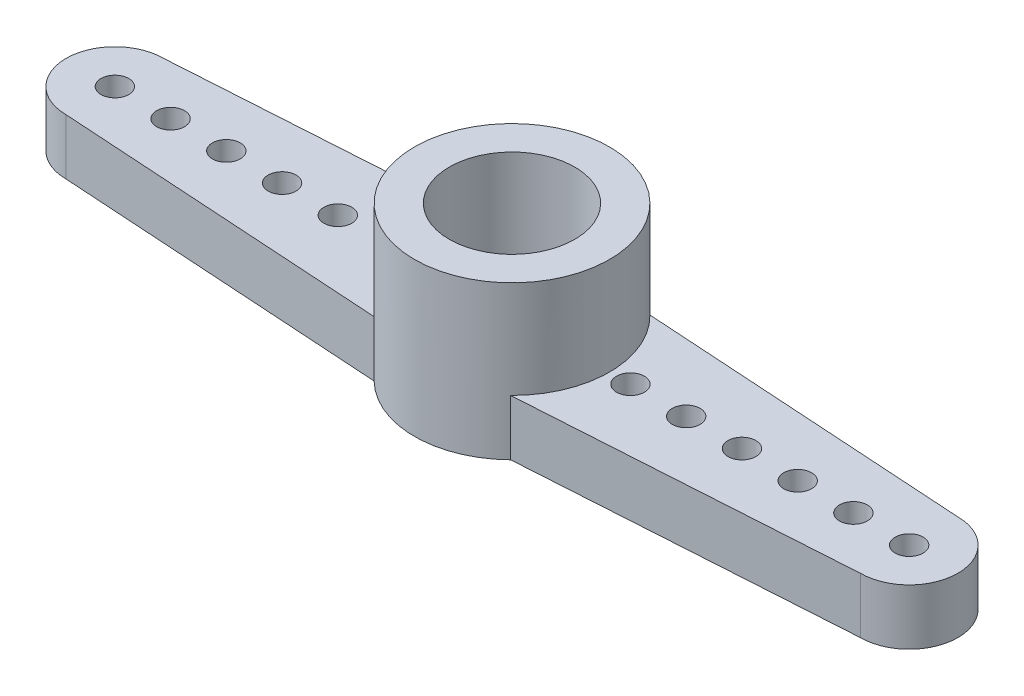
SolidWorks part; units mm, degrees
material "Nylon 101"
ref_plane "Front Plane" through (0, 0, 0) normal (0, 0, 1) x (1, 0, 0)
ref_plane "Top Plane" through (0, 0, 0) normal (0, 1, 0) x (1, 0, 0)
ref_plane "Right Plane" through (0, 0, 0) normal (1, 0, 0) x (0, 0, -1)
sketch "Sketch1" plane through (0, 0, 0) normal (0, 1, 0) x (1, 0, 0)
  line L0 (-16, 0) -> (16, 0) construction
  line L1 (-14.25, 1.75) -> (-2.4495, 2.5)
  line L2 (-14.25, -1.75) -> (-2.4495, -2.5)
  line L3 (-2.4495, 2.5) -> (-2.4495, -2.5) construction
  line L4 (14.25, 1.75) -> (2.4495, 2.5)
  line L5 (14.25, -1.75) -> (2.4495, -2.5)
  line L6 (2.4495, -2.5) -> (2.4495, 2.5) construction
  arc A0 (-2.4495, -2.5) -> (2.4495, -2.5) centre (0, 0) ccw
  arc A1 (14.25, -1.75) -> (14.25, 1.75) centre (14.25, 0) ccw
  arc A2 (-14.25, 1.75) -> (-14.25, -1.75) centre (-14.25, 0) ccw
  arc A3 (2.4495, 2.5) -> (-2.4495, 2.5) centre (0, 0) ccw
  point P14 (0, 0)
  dimension "D1" = 7
  dimension "D2" = 3.5
  dimension "D3" = 32
  dimension "D4" = 5
extrude "Boss-Extrude1" add sketch "Sketch1" along normal blind 2
sketch "Sketch2" plane through (0, 2, 0) normal (0, 1, 0) x (1, 0, 0)
  circle A0 centre (0, 0) radius 2.25
  circle A1 centre (0, 0) radius 3.5
  dimension "D1" = 4.5
  dimension "D2" = 1.25
extrude "Boss-Extrude2" add sketch "Sketch2" along normal blind 3.5
sketch "Sketch3" plane through (0, 2, 0) normal (0, 1, 0) x (1, 0, 0)
  circle A0 centre (0, 0) radius 1.25
  dimension "D1" = 2.5
extrude "Cut-Extrude1" cut sketch "Sketch3" against normal blind 5
sketch "Sketch4" plane through (0, 0, 0) normal (0, -1, 0) x (1, 0, 0)
  circle A0 centre (0, 0) radius 2.5
  dimension "D1" = 5
extrude "Cut-Extrude2" cut sketch "Sketch4" against normal blind 1
sketch "Sketch5" plane through (0, 0, 0) normal (0, -1, 0) x (1, 0, 0)
  line L0 (0, 0) -> (0, 3.5) construction
  line L1 (0, -3.025) -> (0, 3.025) construction
  circle A0 centre (14.25, 0) radius 0.5
  arc A4 (2.4495, 2.5) -> (-2.4495, 2.5) centre (0, 0) ccw construction
  circle A9 centre (12.25, 0) radius 0.5
  circle A10 centre (10.25, 0) radius 0.5
  circle A11 centre (8.25, 0) radius 0.5
  circle A12 centre (6.25, 0) radius 0.5
  circle A13 centre (4.25, 0) radius 0.5
  circle A14 centre (-14.25, 0) radius 0.5
  circle A15 centre (-12.25, 0) radius 0.5
  circle A16 centre (-10.25, 0) radius 0.5
  circle A17 centre (-8.25, 0) radius 0.5
  circle A18 centre (-6.25, 0) radius 0.5
  circle A19 centre (-4.25, 0) radius 0.5
  dimension "D1" = 1
  dimension "D3" = 2
  dimension "D2" = 6
extrude "Cut-Extrude3" cut sketch "Sketch5" against normal blind 5 contours A14 | A0 | A15 | A16 | A17 | A18 | A19 | A13 | A12 | A11 | A10 | A9 region at (14.25, 0, 0) region at (-14.25, 0, 0)
